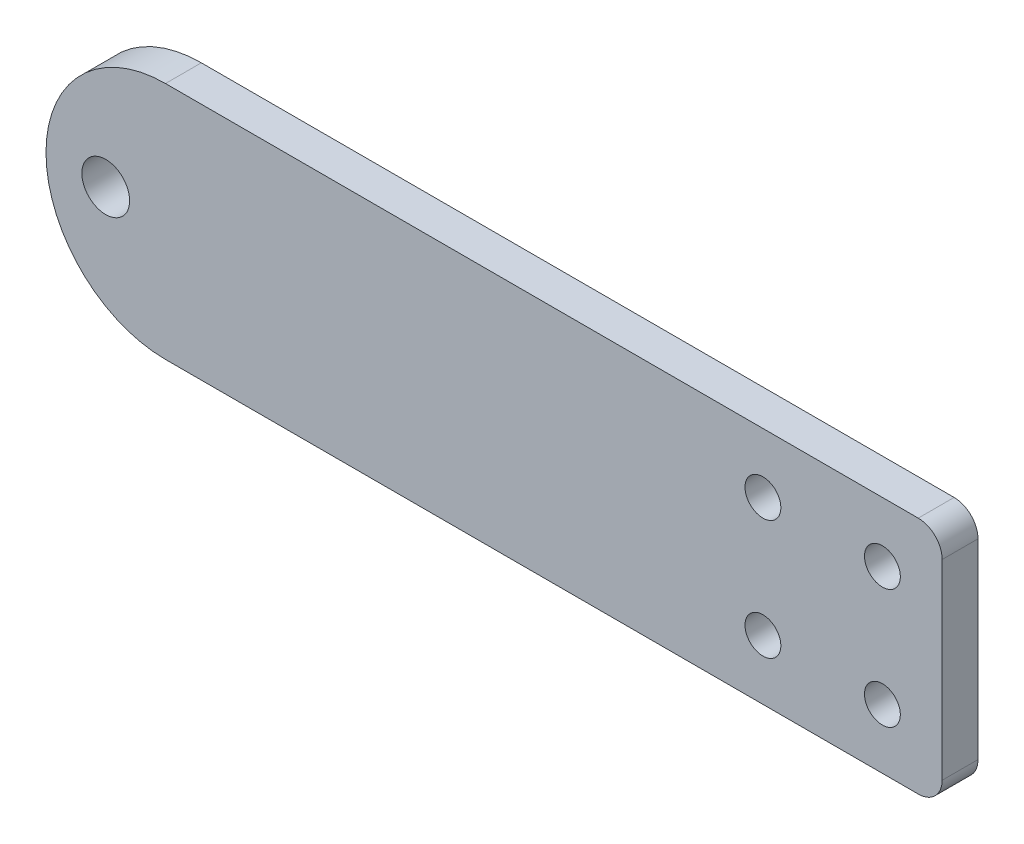
SolidWorks part; units mm, degrees
ref_plane "前视基准面" through (0, 0, 0) normal (0, 0, 1) x (1, 0, 0)
ref_plane "上视基准面" through (0, 0, 0) normal (0, 1, 0) x (1, 0, 0)
ref_plane "右视基准面" through (0, 0, 0) normal (1, 0, 0) x (0, 0, -1)
sketch "草图1" plane through (0, 0, 0) normal (0, 0, 1) x (1, 0, 0)
  line L0 (0, 0) -> (75, 0)
  line L1 (75, 0) -> (75, 20)
  line L2 (75, 20) -> (0, 20)
  line L3 (0, 20) -> (0, 0)
  dimension "D1" = 20
  dimension "D2" = 75
extrude "凸台-拉伸1" add sketch "草图1" along normal blind 3
sketch "草图2" plane through (0, 0, 3) normal (0, 0, 1) x (1, 0, 0)
  line L0 (75, 20) -> (0, 20) construction
  line L1 (75, 0) -> (75, 20) construction
  line L2 (0, 20) -> (0, 0) construction
  circle A0 centre (70, 15) radius 1.5
  circle A1 centre (70, 5) radius 1.5
  circle A2 centre (60, 15) radius 1.5
  circle A3 centre (60, 5) radius 1.5
  circle A4 centre (5, 10) radius 2
  dimension "D1" = 3
  dimension "D2" = 3
  dimension "D3" = 3
  dimension "D4" = 3
  dimension "D9" = 4
  dimension "D5" = 5
  dimension "D6" = 5
  dimension "D7" = 10
  dimension "D8" = 10
  dimension "D10" = 5
  dimension "D11" = 10
extrude "切除-拉伸1" cut sketch "草图2" against normal blind 4
fillet "圆角1" radius 10 2 edges at (0, 0, 1.5) (0, 20, 1.5)
fillet "圆角2" radius 2 2 edges at (75, 0, 1.5) (75, 20, 1.5)
